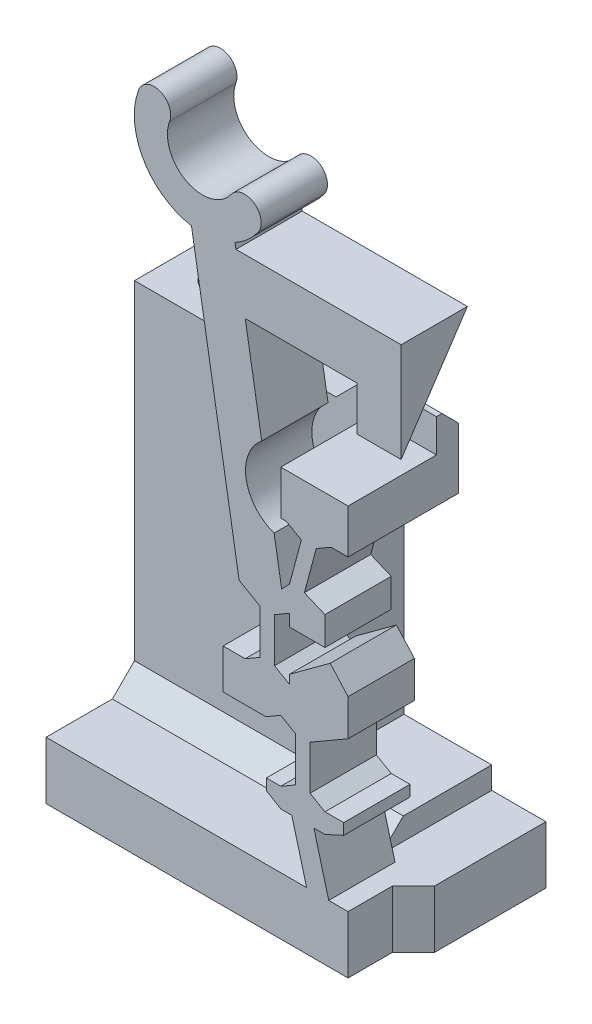
SolidWorks part; units mm, degrees
material "Nylon 6/12"
ref_plane "Front Plane" through (0, 0, 0) normal (0, 0, 1) x (1, 0, 0)
ref_plane "Top Plane" through (0, 0, 0) normal (0, 1, 0) x (1, 0, 0)
ref_plane "Right Plane" through (0, 0, 0) normal (1, 0, 0) x (0, 0, -1)
sketch "Sketch-SkeletonConfigUp" plane through (0, 0, 0) normal (0, 0, 1) x (1, 0, 0)
  line L0 (0, 0) -> (0, -50000) construction
  line L1 (0, 0) -> (4.5811, 6.2164) construction
  line L2 (9.8143, 13.3177) -> (4.5811, 13.945) construction
  line L3 (4.5811, 13.945) -> (2.9713, 10.4094) construction
  line L4 (2.9713, 10.4094) -> (4.5811, 6.2164) construction
  line L5 (4.5811, 13.945) -> (6.2429, 19.1409) construction
  line L6 (2.9713, 10.4094) -> (0.0405, 27.8193) construction
  line L7 (4.5811, 6.2164) -> (9.8143, 13.3177) construction
  line L8 (-587.3593, -797.0242) -> (9.8143, 13.3177) construction
  point P12 (0, 0)
  dimension "D2" = 7.7221
  dimension "D3" = 8.8212
  dimension "D4" = 5.2707
  dimension "D5" = 119.553
  dimension "D6" = 3.8848
  dimension "D7" = 5.4552
  dimension "D8" = 17.6549
  dimension "D9" = 4.4914
  dimension "D10" = 6.745
  dimension "D11" = 145.964
  dimension "D12" = 143.612
sketch "Sketch-SkeletonConfigDown" plane through (0, 0, 0) normal (0, 0, 1) x (1, 0, 0)
  line L0 (0, 0) -> (0, -50000) construction
  line L1 (0, 0) -> (4.5811, 6.2164) construction
  line L2 (9.8143, 13.3177) -> (4.5811, 13.945) construction
  line L3 (4.5811, 13.945) -> (6.1909, 10.4094) construction
  line L4 (6.1909, 10.4094) -> (4.5811, 6.2164) construction
  line L5 (4.5811, 13.945) -> (1.753, 18.6098) construction
  line L6 (6.1909, 10.4094) -> (-8.8652, 19.6294) construction
  line L7 (4.5811, 6.2164) -> (9.8143, 13.3177) construction
  line L8 (-589.9357, -800.5203) -> (9.8143, 13.3177) construction
  dimension "D2" = 7.7221
  dimension "D3" = 8.8212
  dimension "D4" = 5.2707
  dimension "D5" = 119.553
  dimension "D6" = 3.8848
  dimension "D7" = 5.4552
  dimension "D8" = 17.6549
  dimension "D9" = 4.4914
  dimension "D10" = 6.745
  dimension "D11" = 145.964
  dimension "D1" = 143.612
ref_plane "Plane-Cam Base" through (9.128, 0, 0) normal (1, 0, 0) x (0, 0, -1)
ref_plane "Plane-Down-to-Up Derailleur Clearance" through (6.628, 0, 0) normal (1, 0, 0) x (0, 0, -1)
ref_plane "Plane-Cam Cavity Roof" through (5.128, 0, 0) normal (1, 0, 0) x (0, 0, -1)
sketch "Sketch-SwitchBossUp" plane through (0, 0, 0) normal (0, 0, 1) x (1, 0, 0)
  line L0 (3.5811, 11.4759) -> (3.5811, 12.945) construction
  line L5 (5.5811, 12.5552) -> (5.5811, 11.263)
  line L7 (1.5115, 25.1048) -> (1.5536, 24.8548)
  line L8 (-0.4607, 24.7728) -> (1.6966, 11.9577)
  line L9 (2.9713, 10.4094) -> (0.0405, 27.8193) construction
  line L11 (0.1364, 21.2256) -> (2.1086, 21.5576) construction
  line L15 (6.628, -23.7286) -> (6.628, 23.7286) construction
  line L16 (2.9713, 10.4094) -> (4.5811, 6.2164) construction
  line L17 (3.5811, 12.945) -> (3.5811, 14.945) construction
  line L18 (5.5811, 12.945) -> (5.5811, 14.945) construction
  line L19 (4.2561, 13.945) -> (4.9061, 13.945) construction
  line L20 (3.5811, 14.945) -> (5.5811, 14.945) construction
  line L21 (3.5811, 12.945) -> (5.5811, 12.945) construction
  line L22 (4.5811, 12.945) -> (4.5811, 14.945) construction
  line L23 (4.5811, 6.2164) -> (8.5405, 7.1023) construction
  line L24 (1.9713, 9.4094) -> (1.9713, 11.4094) construction
  line L25 (3.9713, 9.4094) -> (3.9713, 11.4094) construction
  line L26 (3.9713, 9.4094) -> (1.9713, 9.4094) construction
  line L27 (1.9713, 11.4094) -> (3.9713, 11.4094) construction
  line L28 (3.5811, 7.2164) -> (5.5811, 7.2164) construction
  line L29 (3.5811, 7.2164) -> (3.5811, 5.2164) construction
  line L30 (5.5811, 7.2164) -> (5.5811, 5.2164) construction
  line L31 (3.5811, 5.2164) -> (5.5811, 5.2164) construction
  line L32 (4.9061, 6.2164) -> (4.2561, 6.2164) construction
  line L40 (3.2963, 10.4094) -> (2.6463, 10.4094) construction
  line L66 (0.0405, 27.8193) -> (0.0405, 50027.8193) construction
  line L75 (4.5811, 3.937) -> (5.251, 1.437) construction
  line L76 (5.5811, 11.263) -> (5.5811, 12.5552) construction
  line L77 (5.5811, 7.6061) -> (6.628, 8.2105)
  line L80 (5.8152, 10.763) -> (6.628, 9.8603)
  line L81 (9.128, 1033.2419) -> (9.128, 20.0586) construction
  line L85 (6.9307, 9.5241) -> (8.5405, 7.7363) construction
  line L88 (5.7256, 17.3347) -> (6.628, 17.3347)
  line L92 (3.7762, 8.3129) -> (6.9307, 9.5241) construction
  line L98 (1.9713, 9.0197) -> (0.9713, 9.0197)
  line L99 (0.9713, 9.0197) -> (0.9713, 7.2164)
  line L100 (0.9713, 7.2164) -> (2.9061, 7.2164)
  line L101 (4.5811, 6.2164) -> (6.9307, 9.5241) construction
  line L103 (0.0405, 27.8193) -> (1.9448, 26.4638) construction
  line L104 (6.9307, 9.5241) -> (8.5405, 7.7363) construction
  line L107 (1.9713, 9.4094) -> (1.9713, 9.0197) construction
  line L109 (0.0405, 27.8193) -> (-2.1498, 28.6358) construction
  line L111 (6.628, 9.8603) -> (6.628, 8.2105)
  line L112 (6.628, 9.8603) -> (6.9307, 9.5241) construction
  line L113 (2.9306, 4.8267) -> (2.9306, 4.3267)
  line L114 (7.3693, 7.7363) -> (7.3563, 7.7363) construction
  line L121 (5.751, -1.0859) -> (5.751, 1.437) construction
  line L122 (9.028, 22.3548) -> (9.028, 20.3548)
  line L127 (5.5811, 15.3347) -> (5.5811, 14.945) construction
  line L133 (2.9713, 10.4094) -> (6.1909, 10.4094) construction
  line L134 (4.5811, 10.4094) -> (4.5811, 13.945) construction
  line L135 (4.5811, 10.4094) -> (4.5811, 6.2164) construction
  line L137 (3.9713, 9.4094) -> (5.5811, 7.2164) construction
  line L139 (5.8152, 10.763) -> (3.9713, 9.4094)
  line L142 (3.0345, 1.437) -> (3.0345, -1.1653)
  line L143 (9.128, 20.0586) -> (9.128, 18.3333) construction
  line L145 (9.128, 16.6071) -> (9.128, -49992.4167) construction
  line L147 (5.5811, 11.263) -> (5.5811, 12.5552) construction
  line L150 (3.0345, -1.1653) -> (6.628, -1.1653)
  line L151 (4.0811, 3.937) -> (5.0811, 3.937) construction
  line L152 (4.5126, 14.945) -> (3.9767, 12.945)
  line L153 (5.1855, 14.945) -> (4.6496, 12.945)
  line L157 (3.5811, 17.3347) -> (3.5811, 15.3347)
  line L158 (5.8605, 15.3347) -> (6.628, 15.3347)
  line L162 (3.2963, 11.4094) -> (3.2963, 9.4094)
  line L164 (2.6463, 11.4094) -> (2.6463, 9.4094)
  line L169 (4.2561, 7.2164) -> (4.2561, 5.2164)
  line L170 (4.9061, 5.2164) -> (4.9061, 7.2164)
  line L175 (4.2561, 7.2164) -> (3.5811, 7.6061)
  line L176 (4.9061, 7.2164) -> (5.5811, 7.6061)
  line L177 (5.5811, 7.2164) -> (5.5811, 7.6061) construction
  line L179 (4.2561, 5.2164) -> (3.5811, 4.8267)
  line L180 (3.5811, 5.2164) -> (3.5811, 4.8267) construction
  line L181 (3.5811, 4.8267) -> (2.9306, 4.8267)
  line L183 (4.9061, 5.2164) -> (5.5811, 4.8267)
  line L184 (5.5811, 5.2164) -> (5.5811, 4.8267) construction
  line L186 (9.128, -23.7286) -> (9.128, 23.7286) construction
  line L187 (2.6463, 9.4094) -> (1.9713, 9.0197)
  line L188 (3.2963, 9.4094) -> (3.9713, 9.0197)
  line L189 (3.2963, 11.4094) -> (3.9713, 11.7991)
  line L190 (2.6463, 11.4094) -> (1.6966, 11.9577)
  line L191 (3.9713, 11.4094) -> (3.9713, 11.7991) construction
  line L192 (3.9713, 11.7991) -> (3.9713, 11.263)
  line L193 (4.6496, 12.945) -> (5.5811, 12.5552)
  line L194 (3.9767, 12.945) -> (3.6203, 12.5779)
  line L195 (3.9713, 11.263) -> (5.5811, 11.263)
  line L196 (3.9713, 9.4094) -> (3.9713, 9.0197)
  line L197 (3.5811, 7.2164) -> (3.5811, 7.6061) construction
  line L199 (3.5811, 7.6061) -> (2.9061, 7.2164)
  line L201 (2.9306, 4.3267) -> (2.9306, 3.937) construction
  line L202 (2.9306, 3.937) -> (4.0811, 3.937) construction
  line L205 (4.0811, 3.937) -> (3.585, 3.937)
  line L207 (9.128, 18.3333) -> (9.128, 16.6071) construction
  line L208 (6.628, -1.1653) -> (6.628, 1.437)
  line L209 (9.128, 20.0586) -> (9.128, 16.6071) construction
  line L211 (5.751, 1.437) -> (5.0811, 3.937)
  line L212 (4.751, 1.437) -> (4.0811, 3.937)
  line L214 (4.5126, 14.945) -> (3.8375, 15.3347)
  line L215 (3.8375, 15.3347) -> (3.5811, 15.3347)
  line L216 (5.1855, 14.945) -> (5.8605, 15.3347)
  line L217 (5.5811, 12.945) -> (5.5811, 12.5552) construction
  line L218 (5.1855, 14.945) -> (5.1855, 15.3347) construction
  line L219 (5.8605, 15.3347) -> (3.8375, 15.3347) construction
  line L221 (9.028, 22.3548) -> (9.028, 24.8548)
  line L224 (3.5811, 17.3347) -> (5.7256, 17.3347)
  line L232 (6.628, 15.3347) -> (6.628, 17.3347)
  line L236 (1.5536, 24.8548) -> (9.028, 24.8548)
  line L240 (5.0811, 3.937) -> (5.5824, 3.937)
  line L241 (5.5824, 3.937) -> (6.4306, 4.3267)
  line L248 (7.028, 22.3548) -> (1.9744, 22.3548)
  line L249 (1.9744, 22.3548) -> (2.7198, 17.9273)
  line L250 (9.028, 20.3548) -> (7.028, 20.3548)
  line L251 (7.028, 20.3548) -> (7.028, 22.3548)
  line L252 (3.2801, 14.5986) -> (3.6203, 12.5779)
  line L253 (4.2672, 14.0291) -> (4.895, 13.8608) construction
  line L254 (5.751, 1.437) -> (4.751, 1.437) construction
  line L255 (4.751, 1.437) -> (3.0345, 1.437) construction
  line L256 (4.5811, 6.2164) -> (4.5811, 3.937) construction
  line L257 (4.751, 1.437) -> (3.0345, 1.437)
  line L259 (5.751, 1.437) -> (6.628, 1.437)
  line L260 (3.585, 3.937) -> (2.9306, 4.3267)
  line L367 (5.5811, 4.8267) -> (6.4306, 4.8267)
  line L368 (6.4306, 4.8267) -> (6.4306, 4.3267)
  arc A0 (1.5115, 25.1048) -> (2.5558, 26.0289) centre (0.0405, 27.8193) ccw
  arc A1 (-0.4607, 24.7728) -> (-2.8525, 28.8978) centre (0.0405, 27.8193) cw
  arc A2 (-2.8525, 28.8978) -> (-1.447, 28.3738) centre (-2.1498, 28.6358) cw
  arc A3 (2.5558, 26.0289) -> (1.3338, 26.8987) centre (1.9448, 26.4638) ccw
  arc A4 (-1.447, 28.3738) -> (1.3338, 26.8987) centre (0.0405, 27.8193) ccw
  arc A5 (3.5811, 12.945) -> (3.5811, 14.945) centre (3.1778, 13.945) ccw construction
  arc A6 (5.5811, 12.945) -> (5.5811, 14.945) centre (5.9843, 13.945) cw construction
  arc A7 (2.528, 9.9183) -> (1.9713, 11.4094) centre (1.568, 10.4094) ccw construction
  arc A8 (3.9713, 11.4094) -> (3.9713, 9.4094) centre (4.3745, 10.4094) ccw construction
  arc A9 (3.5811, 7.2164) -> (3.5811, 5.2164) centre (3.1779, 6.2164) cw construction
  arc A10 (5.5811, 7.2164) -> (5.5811, 5.2164) centre (5.9844, 6.2164) ccw construction
  circle A28 centre (0.0405, 27.8193) radius 2.3375 construction
  arc A29 (1.9713, 9.4094) -> (2.528, 9.9183) centre (1.568, 10.4094) ccw construction
  arc A30 (3.2801, 14.5986) -> (2.7198, 17.9273) centre (3.9114, 16.4164) cw
  point P53 (4.5811, 13.945)
  point P63 (2.9713, 10.4094)
  point P80 (6.628, 1.4306)
  point P93 (1.1225, 21.3916)
  dimension "D23" = 1.5875
  dimension "D24" = 0.75
  dimension "D2" = 2
  dimension "D5" = 2
  dimension "D8" = 42
  dimension "D16" = 42
  dimension "D27" = 120
  dimension "D28" = 120
  dimension "D29" = 120
  dimension "D30" = 120
  dimension "D31" = 120
  dimension "D32" = 120
  dimension "D33" = 120
  dimension "D34" = 120
  dimension "D17" = 0.5
  dimension "D21" = 2
  dimension "D38" = 2
  dimension "D39" = 0.5
  dimension "D40" = 60
  dimension "D41" = 1
  dimension "D42" = 45
  dimension "D43" = 120
  dimension "D10" = 15
  dimension "D25" = 15
  dimension "D26" = 120
  dimension "D35" = 120
  dimension "D83" = 3.5
  dimension "D14" = 2.5
  dimension "D15" = 0.25
  dimension "D7" = 2
  dimension "D9" = 2
  dimension "D6" = 0.65
  dimension "D12" = 1
  dimension "D13" = 18.5
  dimension "D18" = 2.5
  dimension "D19" = 0.65
extrude "Boss-Switch Body" add sketch "Sketch-SwitchBossUp" along normal blind 3
sketch "Sketch1" plane through (0, 0, 0) normal (0, 0, -1) x (-1, 0, 0)
  line L1 (-7.5811, -1.1653) -> (0.4122, -1.1653)
  line L2 (-7.5811, -1.1653) -> (-7.5811, 1.437)
  line L4 (0.4122, -1.1653) -> (0.4122, 1.437)
  line L5 (-3.5811, 18.8347) -> (-7.5811, 18.8347)
  line L10 (-7.5811, 18.8347) -> (-7.5811, 15.3347)
  line L11 (-4.751, 1.437) -> (-5.751, 1.437)
  line L12 (-7.5811, 15.3347) -> (-3.5811, 15.3347)
  line L13 (-4.751, 1.437) -> (-3.0345, 1.437)
  line L14 (-3.5811, 15.3347) -> (-3.5811, 18.8347)
  line L20 (-5.0811, 3.937) -> (-5.751, 1.437) construction
  line L22 (-3.0345, -1.1653) -> (-6.628, -1.1653) construction
  line L23 (-3.0345, 1.437) -> (0.4122, 1.437)
  line L24 (-5.751, 1.437) -> (-6.628, 1.437)
  line L25 (-6.628, 1.437) -> (-7.5811, 1.437)
  point P5 (-6.628, 1.437)
  dimension "D1" = 3.5
extrude "Boss-Flange Width" add sketch "Sketch1" along normal blind 5
ref_plane "Plane-Sta2Sit Groove" through (0.0405, 0, 0) normal (1, 0, 0) x (0, 0, -1)
ref_plane "Plane-Cam Outer Surface" through (-12.0395, 0, 0) normal (1, 0, 0) x (0, 0, -1)
ref_plane "Plane-FlangeTop" through (-7.0395, 0, 0) normal (1, 0, 0) x (0, 0, -1)
sketch "Sketch2" plane through (-7.0395, 0, 0) normal (1, 0, 0) x (0, 0, -1)
  line L0 (5, 15.3347) -> (-3, 15.3347) construction
  line L1 (5, 17.3347) -> (1, 17.3347)
  line L2 (5, 17.3347) -> (5, 15.3347)
  line L3 (5, 15.3347) -> (1, 15.3347)
  line L4 (1, 17.3347) -> (1, 15.3347)
  line L5 (-3, -1.1653) -> (-3, 1.437) construction
  line L11 (5, 1.437) -> (-3, 1.437)
  line L12 (5, 1.437) -> (5, -1.1653)
  line L13 (5, -1.1653) -> (-3, -1.1653)
  line L14 (-3, 1.437) -> (-3, -1.1653)
  line L15 (0, 10.4094) -> (0, 27.8193) construction
  line L17 (5, 1.437) -> (5, -1.1653) construction
  line L18 (-3, 1.437) -> (0, 1.437) construction
  dimension "D1" = 1
  dimension "D2" = 2
extrude "Boss-Flange Height" add sketch "Sketch2" along normal up to surface (11.6675 mm away)
sketch "Sketch10" plane through (0, 15.3347, 0) normal (0, 1, 0) x (1, 0, 0)
  line L0 (9.128, -23.7286) -> (9.128, 23.7286) construction
  line L1 (7.5811, 5) -> (5.128, 5)
  line L2 (7.5811, 5) -> (7.5811, 2)
  line L3 (7.5811, 2) -> (5.128, 2)
  line L5 (4.628, 7) -> (4.628, 1) construction
  line L6 (3.5811, 1) -> (-7.0395, 1) construction
  line L8 (5.128, 5) -> (5.128, 2)
  dimension "D1" = 1
  dimension "D2" = 0.5
  dimension "D3" = 4.5
extrude "Cut-Up-To-Down Derailleur Clearance" cut sketch "Sketch10" along normal up to next
sketch "Sketch17" plane through (0, 15.3347, 0) normal (0, -1, 0) x (1, 0, 0)
  line L0 (5.128, -5) -> (-7.0395, -5)
  line L1 (5.128, -5) -> (-7.0395, -5) construction
  line L2 (-7.0395, -5) -> (-7.0395, -1)
  line L3 (-7.0395, -1) -> (5.128, -1)
  line L4 (5.128, -1) -> (5.128, -5)
  line L5 (-7.0395, -1) -> (-7.0395, -5) construction
extrude "Boss-Flange Support" add sketch "Sketch17" along normal up to surface (13.8977 mm away) up to face at (3.5343, 1.437, 0.2)
sketch "Sketch-HolePositions" plane through (0, -1.1653, 0) normal (0, -1, 0) x (1, 0, 0)
  line L0 (-7.0395, -3) -> (7.5811, -3) construction
  line L1 (7.5811, -5) -> (-7.0395, -5) construction
  line L2 (7.5811, -5) -> (7.5811, 0) construction
  line L4 (-7.0395, -22.2167) -> (-7.0395, 22.2167) construction
  point P6 (-5.0395, -3)
  point P7 (-0.5395, -3)
  dimension "D1" = 2
  dimension "D2" = 4.5
  dimension "D3" = 2
sketch "Sketch6" plane through (0, -1.1653, 0) normal (0, -1, 0) x (-1, 0, 0)
  point P0 (5.0395, 3)
  point P3 (0.5395, 3)
hole_wizard "Tap Drill for M2x0.4 Tap1" positions "Sketch6" profile "Sketch5" hole size "M2x0.4" standard "ANSI Metric" end condition through all
sketch "Sketch5" plane through (-5.0395, -1.1653, -3) normal (1, 0, 0) x (0, 0, -1)
  line L0 (0, 0) -> (0, 30.5511)
  line L1 (0, 30.5511) -> (0.8, 30.5511)
  line L2 (0.8, 30.5511) -> (0.8, 0)
  line L5 (0.8, 0) -> (0, 0)
  line L11 (0, -6.35) -> (0, 107.95) construction
  dimension "Thru Hole Dia." = 1.6
  dimension "Thru Hole Depth" = 30.5511
sketch "Sketch9" plane through (0, -1.1653, 0) normal (0, -1, 0) x (1, 0, 0)
  point P0 (-5.0395, -3)
  point P3 (-0.5395, -3)
hole_wizard "M2 Clearance Hole2" positions "Sketch9" profile "Sketch8" hole size "M2" standard "ANSI Metric"
sketch "Sketch8" plane through (-5.0395, -1.1653, -3) normal (1, 0, 0) x (0, 0, -1)
  line L0 (0, 0) -> (0, 15.721)
  line L1 (0, 15.721) -> (1.2, 15)
  line L2 (1.2, 15) -> (1.2, 0)
  line L5 (1.2, 0) -> (0, 0)
  line L10 (0, 15.721) -> (-1.2, 15) construction
  line L11 (0, -6.35) -> (0, 107.95) construction
  dimension "Hole Dia." = 2.4
  dimension "Hole Depth" = 15
  dimension "Drill Angle" = 118
sketch "Sketch-Measurements for Derailleur Ramps" [suppressed] plane through (0, 0, 0) normal (0, 0, 1) x (1, 0, 0)
  line L0 (3.184, 15.1695) -> (2.4687, 19.4188)
  line L1 (2.8264, 17.2941) -> (1.8402, 17.1281)
  line L2 (2.9713, 10.4094) -> (0.0405, 27.8193) construction
  line L3 (1.8402, 17.1281) -> (-1.3081, 15.0016)
  line L4 (6.1909, 10.4094) -> (-8.8652, 19.6294) construction
  line L5 (1.8402, 17.1281) -> (2.6012, 12.6077)
  line L6 (2.6012, 12.6077) -> (-1.3081, 15.0016)
  line L7 (0.2661, 16.0649) -> (0.2661, 17.1281)
  line L8 (0.2661, 17.1281) -> (1.8402, 17.1281)
  line L9 (6.1909, 10.4094) -> (2.9713, 10.4094)
  line L10 (5.386, 8.3129) -> (3.7762, 8.3129)
  line L11 (2.6116, 18.5698) -> (1.5115, 25.1048) construction
  line L12 (6.1909, 10.4094) -> (4.5811, 6.2164) construction
  line L13 (4.5811, 8.3129) -> (4.5811, 8.7912)
  line L14 (4.5811, 6.2164) -> (5.386, 8.3129)
  line L15 (2.9713, 10.4094) -> (4.5811, 6.2164) construction
  line L16 (3.7762, 8.3129) -> (4.5811, 6.2164)
  line L17 (5.386, 8.3129) -> (5.386, 8.7912)
  dimension "D1" = 1.5742
  dimension "D2" = 0.8049
ref_plane "Plane1" through (0, 7.1023, 0) normal (0, 1, 0) x (1, 0, 0)
ref_plane "Plane-Cantilever Cut" [suppressed] through (7.0848, 8.5204, -1.9058) normal (-0.6301, -0.7578, 0.1695) x (-0.7765, 0.6151, -0.1368)
sketch "Sketch14" [suppressed] plane through (7.0848, 8.5204, -1.9058) normal (-0.6301, -0.7578, 0.1695) x (-0.7765, 0.6151, -0.1368)
  line L0 (2.3023, -1.6911) -> (-0.3551, -1.6911)
  line L2 (2.3023, -4.3362) -> (2.3023, -1.6911)
  line L3 (-0.3551, -1.6911) -> (-0.3551, -4.4608)
  line L5 (-0.3551, -4.4608) -> (1.0087, -5.0843)
  line L6 (1.0087, -5.0843) -> (2.3023, -4.3362)
extrude "Cut-Down-to-Up Cantilever Slope" [suppressed] cut sketch "Sketch14" against normal up to next
ref_plane "Plane-Symmetry Plane" through (0, 0, 1.5) normal (0, 0, 1) x (1, 0, 0)
sketch "Sketch-Cable Center Point" plane through (0, 0, 1.5) normal (0, 0, 1) x (1, 0, 0)
  line L0 (0.0405, 27.8193) -> (0.1722, 27.0366)
  line L1 (2.9713, 10.4094) -> (0.0405, 27.8193) construction
  point P0 (0.0405, 27.8193)
  dimension "D1" = 0.7937
chamfer "Chamfer-Flange Support" distance 1.5 angle 45 1 edges at (3.5811, 17.3347, -3)
chamfer "Chamfer-Flange Support 2" distance 1.5 angle 45 2 edges at (5.128, 17.0847, -2) (5.128, 15.3347, -1.5)
chamfer "Chamfer-Flange Support 3" distance 1 angle 45 1 edges at (-0.9558, 1.437, -1)
chamfer "Chamfer7" [suppressed] distance 1 angle 45
sketch "Sketch23" plane through (0, 0, -1) normal (0, 0, 1) x (1, 0, 0)
  line L0 (5.128, 2.437) -> (1.1605, 2.437)
  line L1 (-7.0395, 2.437) -> (5.128, 2.437) construction
  line L2 (1.1605, 2.437) -> (1.1605, 13.8347)
  line L3 (1.1605, 13.8347) -> (5.128, 13.8347)
  line L4 (5.128, 13.8347) -> (5.128, 2.437)
  line L5 (0.6605, -1.1653) -> (0.6605, 13.8347) construction
  dimension "D1" = 0.5
extrude "Cut-Gap for Printing" cut sketch "Sketch23" against normal through all
sketch "Sketch25" plane through (0, 0, 0) normal (0, 0, 1) x (1, 0, 0)
  line L0 (6.628, 15.3347) -> (7.5811, 15.3347)
  line L1 (7.5811, 15.3347) -> (7.5811, 18.8347)
  line L2 (7.5811, 18.8347) -> (6.628, 18.8347)
  line L3 (6.628, -23.7286) -> (6.628, 23.7286) construction
  line L4 (7.5811, 18.8347) -> (3.5811, 18.8347) construction
  line L5 (6.628, 18.8347) -> (6.628, 15.3347)
  line L6 (7.5811, 18.8347) -> (7.5811, 15.3347) construction
extrude "Cut-Derailleur Clearance" cut sketch "Sketch25" against normal through all
chamfer "Chamfer8" distance 1 angle 45 1 edges at (6.628, 0.1359, 0)
ref_plane "Plane2" through (-3.0866, 5.589, 8.3835) normal (0.2929, -0.5304, -0.7956) x (-0.9561, -0.1625, -0.2437)
sketch "Sketch26" plane through (-3.0866, 5.589, 8.3835) normal (0.2929, -0.5304, -0.7956) x (-0.9561, -0.1625, -0.2437)
  line L0 (-7.553, 20.6804) -> (-7.553, 14.9094)
  line L1 (-12.6703, 20.6804) -> (-5.5238, 20.6804) construction
  line L3 (-7.553, 14.9094) -> (-20.0302, 14.9094)
  line L4 (-20.0302, 14.9094) -> (-20.0302, 20.6804)
  line L5 (-20.0302, 20.6804) -> (-7.553, 20.6804)
extrude "Cut-Up-to-Down Cantilever Slope" cut sketch "Sketch26" along normal up to next
sketch "Sketch27" plane through (5.128, 0, 0) normal (1, 0, 0) x (0, 0, -1)
  line L0 (3.5, 18.8347) -> (3.5, 13.8347) construction
  line L1 (2.5, 18.8347) -> (5, 18.8347)
  line L2 (2.5, 18.8347) -> (2.5, 13.8347)
  line L3 (2.5, 13.8347) -> (5, 13.8347)
  line L4 (5, 18.8347) -> (5, 13.8347)
  dimension "D1" = 1
extrude "Cut-Wide Derailleur Clearance" cut sketch "Sketch27" against normal blind 4 and the other way through all
chamfer "Chamfer9" distance 1.25 angle 45 1 edges at (4.8545, 18.8347, -2.5)
sketch "Sketch28" plane through (0, 0, -1) normal (0, 0, 1) x (1, 0, 0)
  line L0 (3.5811, 18.8347) -> (6.628, 18.8347)
  line L1 (6.628, 18.8347) -> (6.628, 17.3347)
  line L2 (6.628, 17.3347) -> (3.5811, 17.3347)
  line L3 (3.5811, 17.3347) -> (3.5811, 18.8347)
extrude "Cut-Extrude1" cut sketch "Sketch28" along normal up to surface (1 mm away) up to face at (5.1045, 18.0847, 0)
equation "\"axle-diameter\"=2"
equation "\"switch-thickness\"=12"
equation "\"base-width\"=4.0"
equation "\"axle-bushing-radius\"=3"
equation "\"clearance\"= 0.25"
equation "\"arm-width\"=1.5"
equation "\"min-diameter\"=70"
equation "\"alpha\"=143.6120"
equation "\"gamma\"=119.5526"
equation "\"delta\"=145.9637"
equation "\"epsilon\"=6.7452"
equation "\"l_AB\"=8.8212"
equation "\"l_AC\"=4.4914"
equation "\"l_BD\"=5.2707"
equation "\"l_CD\"=3.8848"
equation "\"l_CE\"=17.6549"
equation "\"l_DF\"=5.4552"
equation "\"l_OA\"=7.7221"
equation "\"D2@Sketch-SkeletonConfigUp\" = \"l_OA\""
equation "\"D3@Sketch-SkeletonConfigUp\" = \"l_AB\""
equation "\"D4@Sketch-SkeletonConfigUp\" = \"l_BD\""
equation "\"D5@Sketch-SkeletonConfigUp\" = \"gamma\""
equation "\"D6@Sketch-SkeletonConfigUp\" = \"l_CD\""
equation "\"D7@Sketch-SkeletonConfigUp\" = \"l_DF\""
equation "\"D8@Sketch-SkeletonConfigUp\" = \"l_CE\""
equation "\"D9@Sketch-SkeletonConfigUp\" = \"l_AC\""
equation "\"D_groove\"=3.175"
equation "\"D7@Sketch-SkeletonConfigDown\" = \"l_DF\""
equation "\"D6@Sketch-SkeletonConfigDown\" = \"l_CD\""
equation "\"D2@Sketch-SkeletonConfigDown\" = \"l_OA\""
equation "\"D3@Sketch-SkeletonConfigDown\" = \"l_AB\""
equation "\"D9@Sketch-SkeletonConfigDown\" = \"l_AC\""
equation "\"D8@Sketch-SkeletonConfigDown\" = \"l_CE\""
equation "\"D5@Sketch-SkeletonConfigDown\" = \"gamma\""
equation "\"D4@Sketch-SkeletonConfigDown\" = \"l_BD\""
equation "\"D1@Sketch-SkeletonConfigDown\" = \"alpha\""
equation "\"hinge_length\"=1.5"
equation "\"hinge_depth\"=0.25"
equation "\"D10@Sketch-SkeletonConfigUp\"=\"epsilon\""
equation "\"D11@Sketch-SkeletonConfigUp\"=\"delta\""
equation "\"D12@Sketch-SkeletonConfigUp\"=\"alpha\""
equation "\"D11@Sketch-SkeletonConfigDown\"=\"delta\""
equation "\"D10@Sketch-SkeletonConfigDown\"=\"epsilon\""
equation "\"EE_dx\"=8.9056"
equation "\"EE_dy\"=8.1898"
equation "\"r_groove\"=\"D_groove\"/2"
equation "\"t_wall\"=25.4/16"
equation "\"width_lower\"=\"D_groove\"+\"t_wall\""
equation "\"cable_to_bottom\"=30.6257"
equation "\"switch_EE-up_base_dy\"=24"
equation "\"switch_EE-down_base_dy\"=16"
equation "\"D_axle\"=25.4/8"
equation "\"D_up_to_down\"=16"
equation "\"D_down_to_up\"=25"
equation "\"t_cam_base\"=7.5"
equation "\"D23@Sketch-SwitchBossUp\"=\"D_groove\"/2"
equation "\"D1@Sketch-Cable Center Point\"=\"D_groove\"/4"
